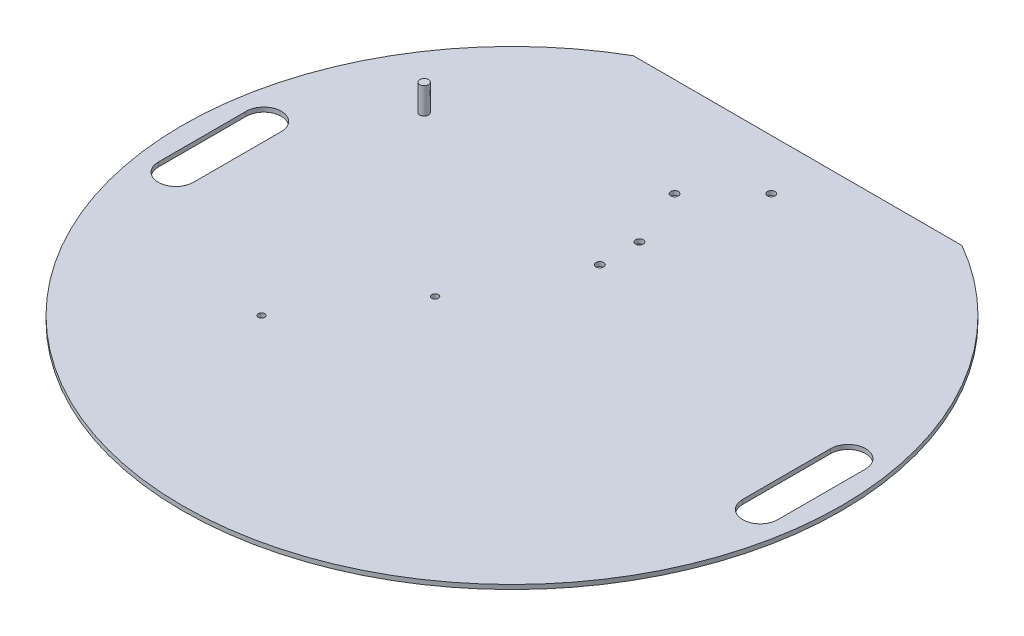
SolidWorks part; units mm, degrees
ref_plane "Face" through (0, 0, 0) normal (0, 0, 1) x (1, 0, 0)
ref_plane "Dessus" through (0, 0, 0) normal (0, 1, 0) x (1, 0, 0)
ref_plane "Droite" through (0, 0, 0) normal (1, 0, 0) x (0, 0, -1)
sketch "Esquisse2" plane through (0, 0, 0) normal (0, 1, 0) x (1, 0, 0)
  line L0 (-120, 90) -> (-120, -90) construction
  line L1 (-150, 0) -> (150, 0) construction
  line L2 (120, 90) -> (120, -90) construction
  line L3 (-74.8331, 130) -> (74.8331, 130)
  arc A0 (-74.8331, 130) -> (74.8331, 130) centre (0, 0) ccw
  dimension "D1" = 300
  dimension "D2" = 120
  dimension "D3" = 120
  dimension "D4" = 130
extrude "Boss.-Extru.1" add sketch "Esquisse2" along normal blind 2
ref_axis "Axe1" through (0, 50, 0) along (0, -1, 0)
ref_axis "Axe2" through (0, 0, 50) along (0, 0, -1)
ref_axis "Axe3" through (80.9, 0, 0) along (-1, 0, 0)
sketch "Esquisse3" plane through (0, 0, 0) normal (0, -1, 0) x (-1, 0, 0)
  line L0 (0, -50) -> (0, 50) construction
  line L1 (-80.9, 0) -> (80.9, 0) construction
  line L2 (125, -20) -> (125, 20)
  line L3 (141, -20) -> (141, 20)
  line L4 (-141, -20) -> (-141, 20)
  line L5 (-125, -20) -> (-125, 20)
  arc A0 (125, -20) -> (141, -20) centre (133, -20) ccw
  arc A1 (141, 20) -> (125, 20) centre (133, 20) ccw
  arc A2 (-141, -20) -> (-125, -20) centre (-133, -20) ccw
  arc A3 (-125, 20) -> (-141, 20) centre (-133, 20) ccw
  circle A4 centre (25, -10) radius 1.5
  circle A5 centre (57, -57) radius 1.5
  circle A6 centre (0, 40) radius 1.75
  circle A7 centre (0, 58) radius 1.75
  circle A8 centre (-11, 107) radius 1.75
  circle A9 centre (11, 85) radius 1.75
  dimension "D1" = 16
  dimension "D2" = 133
  dimension "D3" = 20
  dimension "D4" = 20
  dimension "D5" = 133
  dimension "D6" = 25
  dimension "D7" = 10
  dimension "D8" = 32
  dimension "D9" = 47
  dimension "D10" = 40
  dimension "D11" = 18
  dimension "D12" = 22
  dimension "D13" = 11
  dimension "D14" = 22
  dimension "D15" = 85
extrude "Enlèv. mat.-Extru.1" cut sketch "Esquisse3" against normal through all
sketch "Esquisse4" plane through (0, 2, 0) normal (0, 1, 0) x (1, 0, 0)
  circle A0 centre (-100, 60) radius 2
  dimension "D1" = 60
  dimension "D2" = 100
extrude "Goujon M4x12" add sketch "Esquisse4" along normal blind 12
